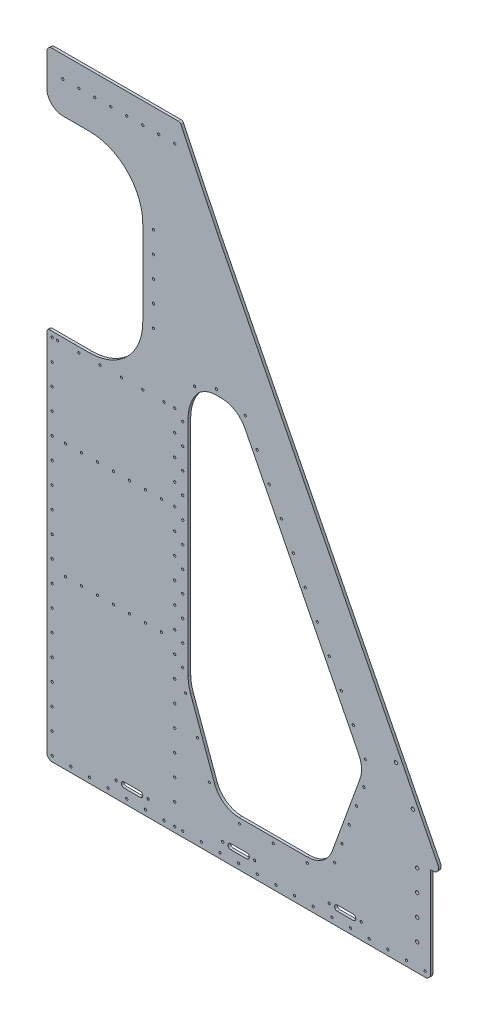
SolidWorks part; units mm, degrees
material "Thornel Mat VMA"
ref_plane "Front Plane" through (0, 0, 0) normal (0, 0, 1) x (1, 0, 0)
ref_plane "Top Plane" through (0, 0, 0) normal (0, 1, 0) x (1, 0, 0)
ref_plane "Right Plane" through (0, 0, 0) normal (1, 0, 0) x (0, 0, -1)
sketch "Sketch1" plane through (0, 0, 0) normal (0, 0, 1) x (1, 0, 0)
  line L1 (-360, -580) -> (360, -580)
  line L2 (-360, -580) -> (-360, 580)
  line L3 (-360, 580) -> (360, 580)
  line L4 (360, -580) -> (360, 580)
  line L5 (-360, -580) -> (360, 580) construction
  line L6 (-360, 580) -> (360, -580) construction
  point P0 (0, 0)
  dimension "D1" = 1160
  dimension "D2" = 720
extrude "Boss-Extrude1" add sketch "Sketch1" along normal blind 5
fillet "Fillet1" radius 10 4 edges at (-360, -580, 2.5) (360, -580, 2.5) (360, 580, 2.5) (-360, 580, 2.5)
sketch "Sketch2" plane through (0, 0, 0) normal (0, 0, -1) x (-1, 0, 0)
  line L0 (-360, -400) -> (110, 580)
  line L2 (-350, 580) -> (350, 580) construction
  line L3 (360, 570) -> (360, -570) construction
  line L4 (-360, -400) -> (-360, 580)
  line L5 (-360, 580) -> (110, 580)
  line L6 (350, -580) -> (-350, -580) construction
  line L7 (-360, -570) -> (-360, 570) construction
  dimension "D1" = 250
  dimension "D2" = 180
extrude "Cut-Extrude1" cut sketch "Sketch2" against normal through all
sketch "Sketch3" plane through (0, 0, 5) normal (0, 0, 1) x (1, 0, 0)
  line L0 (-360, 570) -> (-360, -570) construction
  line L1 (-540, 120) -> (-180, 120)
  line L2 (-540, 120) -> (-540, 480)
  line L3 (-540, 480) -> (-180, 480)
  line L4 (-180, 120) -> (-180, 480)
  line L5 (-540, 120) -> (-180, 480) construction
  line L6 (-540, 480) -> (-180, 120) construction
  line L8 (-350, -580) -> (350, -580) construction
  point P0 (-360, 300)
  dimension "D1" = 180
  dimension "D2" = 360
  dimension "D3" = 700
extrude "Cut-Extrude2" cut sketch "Sketch3" against normal through all
fillet "Fillet2" radius 100 2 edges at (-180, 120, 2.5) (-180, 480, 2.5)
sketch "Sketch4" plane through (0, 0, 0) normal (0, 0, -1) x (-1, 0, 0)
  line L0 (-360, -400) -> (-381.2992, -400)
  line L2 (-381.2992, -400) -> (39.8879, 433.8088)
  line L4 (-360, -400) -> (110, 580) construction
  line L5 (-360, -400) -> (39.8879, 433.8088)
  dimension "D1" = 63.2
  dimension "D2" = 21.2992
  dimension "D3" = 833.8088
extrude "Boss-Extrude2" add sketch "Sketch4" against normal up to surface (5 mm away) up to face at (-147.1893, 59.1378, 5)
fillet "Fillet3" radius 10 1 edges at (381.2992, -400, 2.5)
sketch "Sketch5" plane through (0, 0, 0) normal (0, 0, -1) x (-1, 0, 0)
  line L0 (-360, -410) -> (-335, -410) construction
  line L1 (-365.0445, -400) -> (-360, -400) construction
  line L2 (-360, -570) -> (-360, -400) construction
  line L3 (-335, -410) -> (-335, -557) construction
  circle A0 centre (-335, -410) radius 3
  dimension "D3" = 6
  dimension "D1" = 25
  dimension "D2" = 10
sketch "Sketch6" plane through (0, 0, 0) normal (0, 0, -1) x (-1, 0, 0)
  line L2 (129.1465, 388.7211) -> (-284.7117, -430.579)
  line L3 (155.2883, 440.473) -> (-284.7117, -430.579)
  line L4 (155.2883, 0) -> (155.2883, 440.473)
  line L5 (-284.7117, -430.579) -> (-284.7117, -540.579)
  line L6 (-284.7117, -540.579) -> (115.2883, -540.579)
  line L8 (155.2883, 0) -> (295.2883, 0)
  line L10 (295.2883, 0) -> (295.2883, -540.579)
  line L11 (115.2883, -540.579) -> (295.2883, -540.579)
  dimension "D2" = 110
  dimension "D3" = 580
  dimension "D4" = 140
  dimension "D1" = 100
sketch "Sketch7" plane through (0, 0, 0) normal (0, 0, -1) x (-1, 0, 0)
  line L1 (-255.731, -507.579) -> (-273.0515, -507.579)
  line L2 (-273.0515, -507.579) -> (-281.7117, -522.579)
  line L3 (-281.7117, -522.579) -> (-273.0515, -537.579)
  line L4 (-273.0515, -537.579) -> (-255.731, -537.579)
  line L5 (-255.731, -537.579) -> (-247.0707, -522.579)
  line L6 (-247.0707, -522.579) -> (-255.731, -507.579)
  line L7 (-284.7117, -430.579) -> (-284.7117, -540.579) construction
  line L8 (-284.7117, -540.579) -> (115.2883, -540.579) construction
  circle A0 centre (-264.3912, -522.579) radius 15 construction
  dimension "D1" = 30
  dimension "D2" = 3
  dimension "D3" = 3
sketch "Sketch8" plane through (0, 0, 0) normal (0, 0, -1) x (-1, 0, 0)
  line L0 (-235, -298.898) -> (-157.2605, -145)
  line L1 (-157.2605, -145) -> (27.2605, -145)
  line L3 (27.2605, -145) -> (105, -298.898)
  line L6 (105, -298.898) -> (33.6247, -495)
  line L8 (33.6247, -495) -> (-163.6247, -495)
  line L9 (-163.6247, -495) -> (-235, -298.898)
  line L10 (-65, -145) -> (-65, -495) construction
  line L11 (39.8879, 433.8088) -> (-373.9703, -385.4912) construction
  line L12 (350, -580) -> (-350, -580) construction
  line L13 (-157.2605, -145) -> (1.9373, 170.158) construction
  line L15 (1.9373, 170.158) -> (61.4629, 170.158)
  line L16 (61.4629, 170.158) -> (221.7464, 21.8601)
  line L17 (221.7464, 21.8601) -> (105, -298.898)
  line L18 (-157.2605, -145) -> (1.9373, 170.158)
  line L19 (-360, -570) -> (-360, -400) construction
  arc A0 (180, 220) -> (280, 120) centre (280, 220) ccw construction
  dimension "D2" = 85
  dimension "D3" = 185
  dimension "D4" = 295
  dimension "D1" = 85
  dimension "D5" = 350
  dimension "D6" = 110
  dimension "D7" = 125
extrude "Cut-Extrude5" cut sketch "Sketch8" against normal through all contours L10 L1 L0 L9 L8 | L17 L16 L15 L13 L1 L3 | L1 L10 L8 L6 L3 region at (65, -319.4136, 0) region at (-50.7392, -35.7235, 0)
fillet "Fillet6" radius 50 5 edges at (235, -298.898, 2.5) (-61.4629, 170.158, 2.5) (-221.7464, 21.8601, 2.5) (-33.6247, -495, 2.5) (163.6247, -495, 2.5)
fillet "Fillet7" radius 50 1 edges at (-1.9373, 170.158, 2.5)
sketch "Sketch9" plane through (0, 0, 0) normal (0, 0, -1) x (-1, 0, 0)
  line L0 (110, 100) -> (137.2912, 100)
  line L1 (75.8369, 156.8589) -> (197.3512, 44.4311) construction
  line L2 (110, 100) -> (110, 120)
  line L3 (110, 120) -> (115.6748, 120)
  line L4 (115.6748, 120) -> (137.2912, 100)
  line L6 (280, 120) -> (360, 120) construction
  line L7 (360, 120) -> (360, -570) construction
  line L8 (350, -580) -> (-350, -580) construction
  line L9 (110, 100) -> (130, 100)
  line L10 (110, 100) -> (110, -580)
  line L11 (110, -580) -> (130, -580)
  line L12 (130, 100) -> (130, -580)
  line M26 (75.8369, 156.8589) -> (197.3512, 44.4311)
  line M28 (210.3793, -9.3708) -> (45.599, -462.101)
  dimension "D1" = 20
  dimension "D2" = 250
  dimension "D3" = 20
extrude "Boss-Extrude3" add sketch "Sketch9" against normal up to surface (5 mm away) contours L12 L0 L10 M28 | L3 L2 L0 M26 region at (-119.4227, 107.8143, 0) region at (-119.744, -79.1946, 0) up to face at (-79.8511, 27.8678, 5)
sketch "Sketch10" plane through (0, 0, 0) normal (0, 0, -1) x (-1, 0, 0)
  line L0 (130, -65.1055) -> (110, -65.1055) construction
  line L1 (130, 100) -> (130, -230.2111) construction
  line L2 (110, 120) -> (110, -285.1606) construction
  line L4 (95, -405.1055) -> (145, -405.1055)
  line L5 (95, -405.1055) -> (95, 274.8945)
  line L6 (95, 274.8945) -> (145, 274.8945)
  line L7 (145, -405.1055) -> (145, 274.8945)
  line L8 (95, -405.1055) -> (145, 274.8945) construction
  line L9 (95, 274.8945) -> (145, -405.1055) construction
  point P6 (120, -65.1055)
  dimension "D1" = 50
  dimension "D2" = 680
extrude "Boss-Extrude4" add sketch "Sketch10" against normal up to surface (5 mm away) up to face at (-162.6293, 1.3634, 5)
sketch "Sketch11" plane through (0, 0, 0) normal (0, 0, -1) x (-1, 0, 0)
  line L0 (145, 10.5908) -> (187.7362, 53.3271)
  line L1 (145, -188.9989) -> (145, 92.8676) construction
  line L2 (145, 92.8676) -> (197.3512, 44.4311) construction
  line L3 (187.7362, 53.3271) -> (145, 92.8676)
  line L4 (145, 92.8676) -> (145, 10.5908)
  dimension "D1" = 82.2768
  dimension "D2" = 45
extrude "Boss-Extrude5" add sketch "Sketch11" against normal up to surface (5 mm away) up to face at (-176.4639, -14.7759, 5)
fillet "Fillet8" radius 20 1 edges at (-187.7362, 53.3271, 2.5)
fillet "Fillet9" radius 100 1 edges at (-145, 10.5908, 2.5)
fillet "Fillet10" radius 10 1 edges at (-145, -188.9989, 2.5)
sketch "Sketch12" plane through (0, 0, 0) normal (0, 0, -1) x (-1, 0, 0)
  line L0 (-118.5881, -68.4416) -> (-194.4579, -30.117) construction
  line L1 (-225.2444, -279.5852) -> (-11.9318, 142.7019) construction
  line L2 (39.8879, 433.8088) -> (-373.9703, -385.4912) construction
  line L3 (-127.514, -63.9328) -> (-360, -524.177) construction
  line L4 (-360, -570) -> (-360, -400) construction
  circle A0 centre (-237.7328, -282.129) radius 2.1
  arc A1 (-225.2444, -279.5852) -> (-227.5997, -319.2301) centre (-180.6151, -302.129) ccw construction
  circle A2 centre (-215.1889, -237.4998) radius 2.1
  circle A3 centre (-192.645, -192.8705) radius 2.1
  circle A4 centre (-170.1012, -148.2412) radius 2.1
  circle A5 centre (-147.5573, -103.6119) radius 2.1
  circle A6 centre (-125.0134, -58.9826) radius 2.1
  circle A7 centre (-102.4695, -14.3533) radius 2.1
  circle A8 centre (-79.9257, 30.276) radius 2.1
  circle A9 centre (-57.3818, 74.9053) radius 2.1
  circle A10 centre (-34.8379, 119.5346) radius 2.1
  circle A11 centre (-12.294, 164.1639) radius 2.1
  dimension "D2" = 4.2
  dimension "D1" = 10
  dimension "D3" = 20
  dimension "D5" = 50
  dimension "D4" = 11
extrude "Cut-Extrude6" cut sketch "Sketch12" against normal through all
fillet "Fillet11" radius 80 2 edges at (-95, -326.3728, 2.5) (-95, 139.1288, 2.5)
sketch "Sketch13" plane through (0, 0, 0) normal (0, 0, -1) x (-1, 0, 0)
  circle A0 centre (-295.1195, -258.2984) radius 3.1
  circle A1 centre (-326.9021, -318.4139) radius 3.1
  circle A2 centre (-326.9021, -318.4139) radius 2.25 construction
  circle A3 centre (-295.1195, -258.2984) radius 2.25 construction
  dimension "D1" = 6.2
extrude "Cut-Extrude7" cut sketch "Sketch13" against normal through all
sketch "Sketch14" plane through (0, 0, 5) normal (0, 0, 1) x (1, 0, 0)
  line L0 (-360, 110) -> (-94.8378, 110) construction
  line L1 (-360, 120) -> (-360, -570) construction
  line L2 (-360, 120) -> (-280, 120) construction
  arc A0 (-75.8369, 156.8589) -> (-95, 104.9082) centre (-15, 104.9082) ccw construction
  circle A1 centre (-340, 110) radius 2.1
  circle A2 centre (-300, 110) radius 2.1
  circle A3 centre (-260, 110) radius 2.1
  circle A4 centre (-220, 110) radius 2.1
  circle A5 centre (-180, 110) radius 2.1
  circle A6 centre (-140, 110) radius 2.1
  dimension "D2" = 4.2
  dimension "D3" = 20
  dimension "D5" = 40
  dimension "D1" = 10
  dimension "D4" = 6
extrude "Cut-Extrude8" cut sketch "Sketch14" against normal through all
sketch "Sketch15" plane through (0, 0, 5) normal (0, 0, 1) x (1, 0, 0)
  line L0 (-350, 120) -> (-350, -580) construction
  line L1 (-360, 120) -> (-280, 120) construction
  line L2 (-360, 120) -> (-360, -570) construction
  line L3 (-350, -580) -> (350, -580) construction
  line L4 (-120, 120) -> (-120, -580) construction
  arc A0 (-360, -570) -> (-350, -580) centre (-350, -570) ccw construction
  circle A1 centre (-350, -570) radius 2.1
  circle A2 centre (-350, -530) radius 2.1
  circle A3 centre (-350, -490) radius 2.1
  circle A4 centre (-350, -450) radius 2.1
  circle A5 centre (-350, -410) radius 2.1
  circle A6 centre (-350, -370) radius 2.1
  circle A7 centre (-350, -330) radius 2.1
  circle A8 centre (-350, -290) radius 2.1
  circle A9 centre (-350, -250) radius 2.1
  circle A10 centre (-350, -210) radius 2.1
  circle A11 centre (-350, -170) radius 2.1
  circle A12 centre (-350, -130) radius 2.1
  circle A13 centre (-350, -90) radius 2.1
  circle A14 centre (-350, -50) radius 2.1
  circle A15 centre (-350, -10) radius 2.1
  circle A16 centre (-350, 30) radius 2.1
  circle A17 centre (-350, 70) radius 2.1
  circle A18 centre (-350, 110) radius 2.1
  circle A19 centre (-120, -570) radius 2.1
  circle A20 centre (-120, -530) radius 2.1
  circle A21 centre (-120, -490) radius 2.1
  circle A22 centre (-120, -450) radius 2.1
  circle A23 centre (-120, -410) radius 2.1
  circle A24 centre (-120, -370) radius 2.1
  circle A25 centre (-120, -330) radius 2.1
  circle A26 centre (-120, -290) radius 2.1
  circle A27 centre (-120, -250) radius 2.1
  circle A28 centre (-120, -210) radius 2.1
  circle A29 centre (-120, -170) radius 2.1
  circle A30 centre (-120, -130) radius 2.1
  circle A31 centre (-120, -90) radius 2.1
  circle A32 centre (-120, -50) radius 2.1
  circle A33 centre (-120, -10) radius 2.1
  circle A34 centre (-120, 30) radius 2.1
  circle A35 centre (-120, 70) radius 2.1
  circle A36 centre (-120, 110) radius 2.1
  dimension "D2" = 10
  dimension "D3" = 4.2
  dimension "D5" = 40
  dimension "D1" = 10
  dimension "D7" = 230
  dimension "D4" = 18
  dimension "D6" = 2
extrude "Cut-Extrude9" cut sketch "Sketch15" against normal through all
sketch "Sketch16" plane through (0, 0, 5) normal (0, 0, 1) x (1, 0, 0)
  line L0 (-360, -570) -> (360, -570) construction
  line L1 (-360, 120) -> (-360, -570) construction
  line L2 (360, -570) -> (360, -400) construction
  line L3 (-350, -580) -> (350, -580) construction
  circle A0 centre (-315, -570) radius 2.1
  circle A1 centre (-350, -570) radius 2.1 construction
  circle A2 centre (-280, -570) radius 2.1
  circle A3 centre (-245, -570) radius 2.1
  circle A4 centre (-210, -570) radius 2.1
  circle A5 centre (-175, -570) radius 2.1
  circle A6 centre (-140, -570) radius 2.1
  circle A7 centre (-105, -570) radius 2.1
  circle A8 centre (-70, -570) radius 2.1
  circle A9 centre (-35, -570) radius 2.1
  circle A10 centre (0, -570) radius 2.1
  circle A11 centre (35, -570) radius 2.1
  circle A12 centre (70, -570) radius 2.1
  circle A13 centre (105, -570) radius 2.1
  circle A14 centre (140, -570) radius 2.1
  circle A15 centre (175, -570) radius 2.1
  circle A16 centre (210, -570) radius 2.1
  circle A17 centre (245, -570) radius 2.1
  circle A18 centre (280, -570) radius 2.1
  circle A19 centre (315, -570) radius 2.1
  circle A20 centre (350, -570) radius 2.1
  dimension "D2" = 35
  dimension "D3" = 4.2
  dimension "D5" = 35
  dimension "D1" = 10
  dimension "D4" = 20
extrude "Cut-Extrude10" cut sketch "Sketch16" against normal through all
sketch "Sketch17" plane through (0, 0, 0) normal (0, 0, -1) x (-1, 0, 0)
  circle A0 centre (-335, -410) radius 3.1
  circle A1 centre (-335, -450) radius 3.1
  circle A2 centre (-335, -490) radius 3.1
  circle A3 centre (-335, -530) radius 3.1
  dimension "D1" = 6.2
extrude "Cut-Extrude11" cut sketch "Sketch17" against normal through all
sketch "Sketch18" plane through (0, 0, 0) normal (0, 0, -1) x (-1, 0, 0)
  line L4 (-184.9959, -465.5212) -> (-236.9967, -322.6503)
  line L5 (-184.9959, -465.5212) -> (-236.9967, -322.6503) construction
  line L7 (-1.3857, -505) -> (-128.6143, -505)
  line L8 (-1.3857, -505) -> (-128.6143, -505) construction
  line L10 (99.5723, -343.0484) -> (54.9959, -465.5212)
  line L11 (99.5723, -343.0484) -> (54.9959, -465.5212) construction
  line L13 (105, 104.9082) -> (105, -312.2666)
  line L14 (105, 104.9082) -> (105, -312.2666) construction
  line L16 (41.8804, 180.158) -> (32.6975, 180.158)
  line L17 (41.8804, 180.158) -> (32.6975, 180.158) construction
  circle A0 centre (-234.9445, -328.2884) radius 2.1
  circle A1 centre (-221.2637, -365.8761) radius 2.1
  circle A2 centre (-207.5829, -403.4638) radius 2.1
  circle A3 centre (-193.9021, -441.0515) radius 2.1
  circle A4 centre (-180.2213, -478.6392) radius 2.1
  circle A8 centre (-128.6143, -505) radius 2.1
  circle A9 centre (-65, -505) radius 2.1
  circle A10 centre (-1.3857, -505) radius 2.1
  circle A11 centre (54.9959, -465.5212) radius 2.1
  circle A12 centre (77.2841, -404.2848) radius 2.1
  circle A13 centre (99.5723, -343.0484) radius 2.1
  circle A15 centre (105, -304.2666) radius 2.1
  circle A16 centre (105, -264.2666) radius 2.1
  circle A17 centre (105, -224.2666) radius 2.1
  circle A18 centre (105, -184.2666) radius 2.1
  circle A19 centre (105, -144.2666) radius 2.1
  circle A20 centre (105, -104.2666) radius 2.1
  circle A21 centre (105, -64.2666) radius 2.1
  circle A22 centre (105, -24.2666) radius 2.1
  circle A23 centre (105, 15.7334) radius 2.1
  circle A24 centre (105, 55.7334) radius 2.1
  circle A25 centre (105, 95.7334) radius 2.1
  circle A33 centre (41.8804, 180.158) radius 2.1
  circle A34 centre (82.6282, 164.1991) radius 2.1
  arc A35 (82.6282, 164.1991) -> (41.8804, 180.158) centre (41.8804, 120.158) ccw
  arc A36 (32.6975, 180.158) -> (-20.8577, 147.2107) centre (32.6975, 120.158) ccw
  arc A37 (82.6282, 164.1991) -> (41.8804, 180.158) centre (41.8804, 120.158) ccw construction
  arc A38 (32.6975, 180.158) -> (-20.8577, 147.2107) centre (32.6975, 120.158) ccw construction
  circle A41 centre (105, 135.7334) radius 2.1 [skipped]
  dimension "D2" = 6
  dimension "D3" = 4.2
  dimension "D5" = 40
  dimension "D9" = 8
  dimension "D11" = 40
  dimension "D1" = 10
  dimension "D6" = 10
  dimension "D7" = 10
  dimension "D8" = 10
  dimension "D12" = 10
  dimension "D4" = 5
  dimension "D10" = 12
extrude "Cut-Extrude12" cut sketch "Sketch18" against normal through all
sketch "Sketch19" plane through (0, 0, 0) normal (0, 0, -1) x (-1, 0, 0)
  line L2 (160, 220) -> (160, 380)
  line L3 (160, 220) -> (160, 380) construction
  circle A0 centre (160, 380) radius 2.1
  circle A1 centre (160, 340) radius 2.1
  circle A2 centre (160, 300) radius 2.1
  circle A3 centre (160, 260) radius 2.1
  circle A4 centre (160, 220) radius 2.1
  dimension "D2" = 4.2
  dimension "D4" = 40
  dimension "D1" = 20
  dimension "D3" = 5
extrude "Cut-Extrude13" cut sketch "Sketch19" against normal through all
sketch "Sketch20" plane through (0, 0, 5) normal (0, 0, 1) x (1, 0, 0)
  line L0 (-145, -30.8253) -> (-145, -132.2861) construction
  line L1 (-213.3947, 45.1358) -> (-145, 45.1358)
  line L2 (-213.3947, 45.1358) -> (-213.3947, -142.2861)
  line L3 (-213.3947, -142.2861) -> (-145, -142.2861)
  line L4 (-145, 45.1358) -> (-145, -142.2861)
  arc A0 (-173.6871, 39.2779) -> (-204.1189, 36.7395) centre (-187.8292, 25.1358) ccw construction
  arc A1 (-164.3969, -135.7063) -> (-145, -132.2861) centre (-155, -132.2861) ccw construction
  arc A2 (-204.1189, 36.7395) -> (-210.3793, -9.3708) centre (-163.3947, 7.7302) ccw construction
extrude "Boss-Extrude6" add sketch "Sketch20" against normal up to surface (5 mm away) up to face at (-162.1, 380, 0)
fillet "Fillet12" radius 30 1 edges at (-360, 480, 2.5)
sketch "Sketch22" plane through (0, 0, 0) normal (0, 0, -1) x (-1, 0, 0)
  line L0 (-215, -550) -> (-185, -550) construction
  line L1 (-215, -545) -> (-185, -545)
  line L2 (-215, -555) -> (-185, -555)
  line L4 (-335, -410) -> (-335, -557) construction
  line L5 (-200, -550) -> (-200, -545) construction
  line L6 (0, -550) -> (0, -545) construction
  line L7 (-15, -550) -> (15, -550) construction
  line L8 (-15, -545) -> (15, -545)
  line L9 (-15, -555) -> (15, -555)
  line L10 (200, -550) -> (200, -545) construction
  line L11 (185, -550) -> (215, -550) construction
  line L12 (185, -545) -> (215, -545)
  line L13 (185, -555) -> (215, -555)
  arc A0 (-215, -545) -> (-215, -555) centre (-215, -550) ccw
  arc A1 (-185, -555) -> (-185, -545) centre (-185, -550) ccw
  circle A3 centre (-210, -570) radius 2.1 construction
  circle A4 centre (-230, -550) radius 2.1
  circle A5 centre (-170, -550) radius 2.1
  circle A6 centre (-30, -550) radius 2.1
  circle A7 centre (30, -550) radius 2.1
  arc A8 (-15, -545) -> (-15, -555) centre (-15, -550) ccw
  arc A9 (15, -555) -> (15, -545) centre (15, -550) ccw
  circle A10 centre (170, -550) radius 2.1
  circle A11 centre (230, -550) radius 2.1
  arc A12 (185, -545) -> (185, -555) centre (185, -550) ccw
  arc A13 (215, -555) -> (215, -545) centre (215, -550) ccw
  point P2 (-200, -550)
  point P21 (0, -550)
  point P32 (200, -550)
  dimension "D1" = 5
  dimension "D3" = 4.2
  dimension "D4" = 15
  dimension "D6" = 135
  dimension "D2" = 30
  dimension "D5" = 20
  dimension "D7" = 3
  dimension "D8" = 200
extrude "Cut-Extrude14" cut sketch "Sketch22" against normal through all
fillet "Fillet13" radius 5 2 edges at (-360, 120, 2.5) (-110, 580, 2.5)
sketch "Sketch26" plane through (0, 0, 0) normal (0, 0, -1) x (-1, 0, 0)
  line L0 (360, 540) -> (90.8163, 540) construction
  line L1 (360, 570) -> (360, 510) construction
  line L2 (39.8879, 433.8088) -> (108.639, 577.1622) construction
  circle A0 centre (120, 540) radius 2.1
  circle A1 centre (150, 540) radius 2.1
  circle A2 centre (180, 540) radius 2.1
  circle A3 centre (210, 540) radius 2.1
  circle A4 centre (240, 540) radius 2.1
  circle A5 centre (270, 540) radius 2.1
  circle A6 centre (300, 540) radius 2.1
  circle A7 centre (330, 540) radius 2.1
  dimension "D1" = 240
  dimension "D2" = 4.2
  dimension "D4" = 30
  dimension "D3" = 8
extrude "Cut-Extrude15" cut sketch "Sketch26" against normal through all
sketch "Sketch27" plane through (0, 0, 0) normal (0, 0, -1) x (-1, 0, 0)
  line L0 (360, -50) -> (95, -50) construction
  line L1 (360, 115) -> (360, -570) construction
  line L2 (95, 104.9082) -> (95, -312.2666) construction
  line L3 (280, 120) -> (355, 120) construction
  line L4 (95, -266.5) -> (360, -266.5) construction
  circle A0 centre (145, -50) radius 2.1
  circle A1 centre (120, -50) radius 2.1 construction
  circle A2 centre (325, -50) radius 2.1
  circle A3 centre (350, -50) radius 2.1 construction
  circle A4 centre (175, -50) radius 2.1
  circle A5 centre (205, -50) radius 2.1
  circle A6 centre (235, -50) radius 2.1
  circle A7 centre (265, -50) radius 2.1
  circle A8 centre (295, -50) radius 2.1
  circle A9 centre (325, -50) radius 2.1
  circle A10 centre (145, -266.5) radius 2.1
  circle A11 centre (175, -266.5) radius 2.1
  circle A12 centre (205, -266.5) radius 2.1
  circle A13 centre (235, -266.5) radius 2.1
  circle A14 centre (295, -266.5) radius 2.1
  circle A15 centre (265, -266.5) radius 2.1
  circle A16 centre (325, -266.5) radius 2.1
  point P18 (0, 0)
  dimension "D3" = 25
  dimension "D4" = 25
  dimension "D6" = 30
  dimension "D1" = 170
  dimension "D2" = 386.5
  dimension "D5" = 7
  dimension "D7" = 2
extrude "Cut-Extrude16" cut sketch "Sketch27" against normal through all contours A0 | A4 | A7 | A8 | A2 | A10 | A11 | A12 | A13 | A15 | A14 | A16 | A5 | A6 region at (-145, -50, 0) region at (-325, -50, 0) region at (-175, -50, 0) region at (-265, -50, 0) region at (-295, -50, 0) region at (-145, -266.5, 0) region at (-175, -266.5, 0) region at (-205, -266.5, 0) region at (-235, -266.5, 0) region at (-295, -266.5, 0) region at (-265, -266.5, 0) region at (-325, -266.5, 0)
